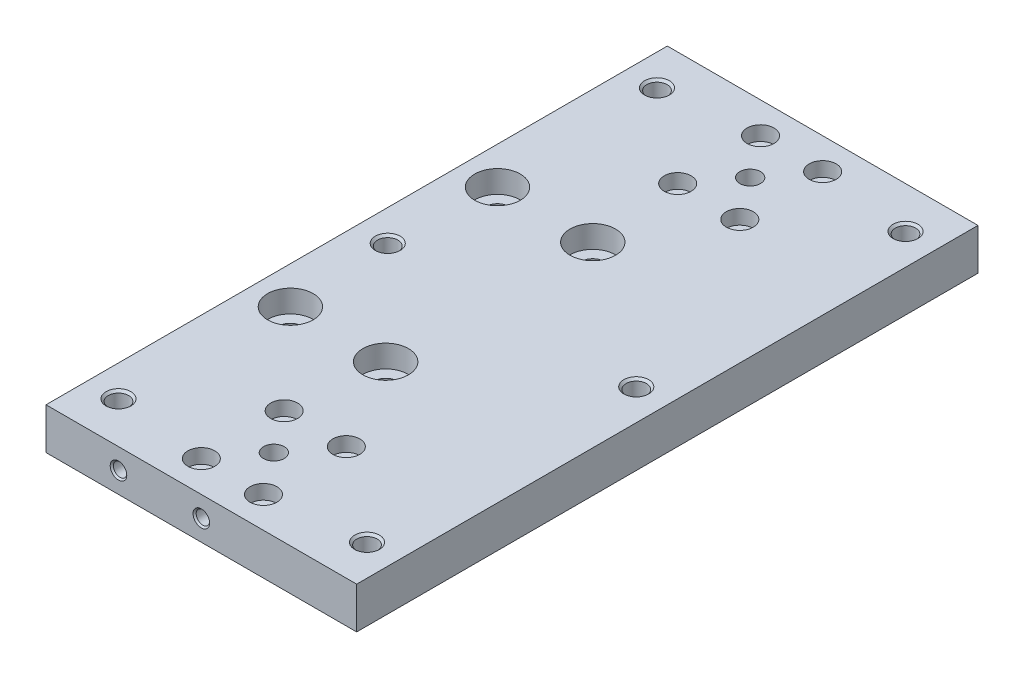
SolidWorks part; units mm, degrees
ref_plane "前视基准面" through (0, 0, 0) normal (0, 0, 1) x (1, 0, 0)
ref_plane "上视基准面" through (0, 0, 0) normal (0, 1, 0) x (1, 0, 0)
ref_plane "右视基准面" through (0, 0, 0) normal (1, 0, 0) x (0, 0, -1)
sketch "草图1" plane through (0, 0, 0) normal (0, 0, 1) x (1, 0, 0)
  line L0 (-37.5, 0) -> (37.5, 0)
  line L1 (37.5, 0) -> (37.5, 10)
  line L2 (37.5, 10) -> (-37.5, 10)
  line L3 (-37.5, 10) -> (-37.5, 0)
extrude "凸台-拉伸1" add sketch "草图1" against normal blind 75 and the other way blind 75
ref_plane "基准面4" through (0, 0, 57.5) normal (0, 0, 1) x (1, 0, 0)
sketch "草图2" plane through (0, 0, 57.5) normal (0, 0, 1) x (1, 0, 0)
  line L0 (0, 0) -> (-2.5, 0)
  line L1 (-2.5, 0) -> (-2.5, 10)
  line L2 (-2.5, 10) -> (0, 10)
  line L3 (0, 10) -> (0, 0)
  line L4 (0, 10) -> (0, 0) construction
revolve "切除-旋转1" cut sketch "草图2" angle 360 about L4 reverse direction yes
ref_plane "基准面5" through (0, 0, -57.5) normal (0, 0, 1) x (1, 0, 0)
sketch "草图3" plane through (0, 0, -57.5) normal (0, 0, 1) x (1, 0, 0)
  line L0 (0, 0) -> (-2.5, 0)
  line L1 (-2.5, 0) -> (-2.5, 10)
  line L2 (-2.5, 10) -> (0, 10)
  line L3 (0, 10) -> (0, 0)
  line L4 (0, 10) -> (0, 0) construction
revolve "切除-旋转2" cut sketch "草图3" angle 360 about L4 reverse direction yes
ref_plane "基准面6" through (0, 0, 67.5) normal (0, 0, 1) x (1, 0, 0)
sketch "草图4" plane through (0, 0, 67.5) normal (0, 0, 1) x (1, 0, 0)
  line L0 (-7.5, 0) -> (-9.25, 0)
  line L1 (-9.25, 0) -> (-9.25, 6.5)
  line L2 (-9.25, 6.5) -> (-10.75, 6.5)
  line L3 (-10.75, 6.5) -> (-10.75, 10)
  line L4 (-10.75, 10) -> (-7.5, 10)
  line L5 (-7.5, 10) -> (-7.5, 0)
  line L6 (-7.5, 10) -> (-7.5, 0) construction
revolve "切除-旋转3" cut sketch "草图4" angle 360 about L6 reverse direction yes
ref_plane "基准面7" through (0, 0, -47.5) normal (0, 0, 1) x (1, 0, 0)
ref_plane "基准面8" through (0, 0, -47.5) normal (0, 0, 1) x (1, 0, 0)
ref_plane "基准面9" through (0, 0, -67.5) normal (0, 0, 1) x (1, 0, 0)
ref_plane "基准面10" through (0, 0, -67.5) normal (0, 0, 1) x (1, 0, 0)
ref_plane "基准面11" through (0, 0, 47.5) normal (0, 0, 1) x (1, 0, 0)
ref_plane "基准面12" through (0, 0, 47.5) normal (0, 0, 1) x (1, 0, 0)
ref_plane "基准面13" through (0, 0, 67.5) normal (0, 0, 1) x (1, 0, 0)
sketch "草图6" plane through (0, 0, -47.5) normal (0, 0, 1) x (1, 0, 0)
  line L0 (7.5, 0) -> (5.75, 0)
  line L1 (5.75, 0) -> (5.75, 6.5)
  line L2 (5.75, 6.5) -> (4.25, 6.5)
  line L3 (4.25, 6.5) -> (4.25, 10)
  line L4 (4.25, 10) -> (7.5, 10)
  line L5 (7.5, 10) -> (7.5, 0)
  line L6 (7.5, 10) -> (7.5, 0) construction
sketch "草图7" plane through (0, 0, -47.5) normal (0, 0, 1) x (1, 0, 0)
  line L0 (-7.5, 0) -> (-9.25, 0)
  line L1 (-9.25, 0) -> (-9.25, 6.5)
  line L2 (-9.25, 6.5) -> (-10.75, 6.5)
  line L3 (-10.75, 6.5) -> (-10.75, 10)
  line L4 (-10.75, 10) -> (-7.5, 10)
  line L5 (-7.5, 10) -> (-7.5, 0)
  line L6 (-7.5, 10) -> (-7.5, 0) construction
sketch "草图8" plane through (0, 0, -67.5) normal (0, 0, 1) x (1, 0, 0)
  line L0 (7.5, 0) -> (5.75, 0)
  line L1 (5.75, 0) -> (5.75, 6.5)
  line L2 (5.75, 6.5) -> (4.25, 6.5)
  line L3 (4.25, 6.5) -> (4.25, 10)
  line L4 (4.25, 10) -> (7.5, 10)
  line L5 (7.5, 10) -> (7.5, 0)
  line L6 (7.5, 10) -> (7.5, 0) construction
sketch "草图9" plane through (0, 0, -67.5) normal (0, 0, 1) x (1, 0, 0)
  line L0 (-7.5, 0) -> (-9.25, 0)
  line L1 (-9.25, 0) -> (-9.25, 6.5)
  line L2 (-9.25, 6.5) -> (-10.75, 6.5)
  line L3 (-10.75, 6.5) -> (-10.75, 10)
  line L4 (-10.75, 10) -> (-7.5, 10)
  line L5 (-7.5, 10) -> (-7.5, 0)
  line L6 (-7.5, 10) -> (-7.5, 0) construction
sketch "草图10" plane through (0, 0, 47.5) normal (0, 0, 1) x (1, 0, 0)
  line L0 (7.5, 0) -> (5.75, 0)
  line L1 (5.75, 0) -> (5.75, 6.5)
  line L2 (5.75, 6.5) -> (4.25, 6.5)
  line L3 (4.25, 6.5) -> (4.25, 10)
  line L4 (4.25, 10) -> (7.5, 10)
  line L5 (7.5, 10) -> (7.5, 0)
  line L6 (7.5, 10) -> (7.5, 0) construction
sketch "草图11" plane through (0, 0, 47.5) normal (0, 0, 1) x (1, 0, 0)
  line L0 (-7.5, 0) -> (-9.25, 0)
  line L1 (-9.25, 0) -> (-9.25, 6.5)
  line L2 (-9.25, 6.5) -> (-10.75, 6.5)
  line L3 (-10.75, 6.5) -> (-10.75, 10)
  line L4 (-10.75, 10) -> (-7.5, 10)
  line L5 (-7.5, 10) -> (-7.5, 0)
  line L6 (-7.5, 10) -> (-7.5, 0) construction
sketch "草图12" plane through (0, 0, 67.5) normal (0, 0, 1) x (1, 0, 0)
  line L0 (7.5, 0) -> (5.75, 0)
  line L1 (5.75, 0) -> (5.75, 6.5)
  line L2 (5.75, 6.5) -> (4.25, 6.5)
  line L3 (4.25, 6.5) -> (4.25, 10)
  line L4 (4.25, 10) -> (7.5, 10)
  line L5 (7.5, 10) -> (7.5, 0)
  line L6 (7.5, 10) -> (7.5, 0) construction
revolve "切除-旋转4" cut sketch "草图6" angle 360 about L6 reverse direction yes
revolve "切除-旋转5" cut sketch "草图7" angle 360 about L6 reverse direction yes
revolve "切除-旋转6" cut sketch "草图8" angle 360 about L6 reverse direction yes
revolve "切除-旋转7" cut sketch "草图9" angle 360 about L6 reverse direction yes
revolve "切除-旋转8" cut sketch "草图10" angle 360 about L6 reverse direction yes
revolve "切除-旋转9" cut sketch "草图11" angle 360 about L6 reverse direction yes
revolve "切除-旋转10" cut sketch "草图12" angle 360 about L6 reverse direction yes
ref_plane "基准面14" through (0, 6.5, 0) normal (0, 1, 0) x (1, 0, 0)
ref_plane "基准面15" through (-28.5, 0, 0) normal (1, 0, 0) x (0, 0, -1)
sketch "草图13" plane through (-28.5, 0, 0) normal (1, 0, 0) x (0, 0, -1)
  line L0 (-25, 0) -> (-27.75, 0)
  line L1 (-27.75, 0) -> (-27.75, 4.6)
  line L2 (-27.75, 4.6) -> (-30.5, 4.6)
  line L3 (-30.5, 4.6) -> (-30.5, 10)
  line L4 (-30.5, 10) -> (-25, 10)
  line L5 (-25, 10) -> (-25, 0)
  line L6 (-25, 10) -> (-25, 0) construction
revolve "切除-旋转11" cut sketch "草图13" angle 360 about L6 reverse direction yes
sketch "草图14" plane through (0, 0, 0) normal (0, 1, 0) x (1, 0, 0)
  line L0 (-28.5, -25) -> (971.5, -25)
  line L1 (-28.5, -25) -> (-28.5, 975)
pattern_linear "阵列(线性)2" count 2 spacing 23 along (1, 0, 0) count 2 spacing 50 along (0, 0, -1) of "切除-旋转11"
ref_plane "基准面16" through (0, 4.6, 0) normal (0, 1, 0) x (1, 0, 0)
ref_plane "基准面17" through (0, 2.5, 0) normal (0, 1, 0) x (1, 0, 0)
sketch "草图15" plane through (0, 2.5, 0) normal (0, 1, 0) x (1, 0, 0)
  line L0 (-36.5, 32.5) -> (-36.5, -32.5)
  line L1 (-36.5, -32.5) -> (2.5, -32.5)
  line L2 (2.5, -32.5) -> (2.5, 32.5)
  line L3 (2.5, 32.5) -> (-36.5, 32.5)
extrude "切除-拉伸1" cut sketch "草图15" against normal blind 32.5
ref_plane "基准面18" through (0, 0, 0) normal (1, 0, 0) x (0, 0, -1)
sketch "草图16" plane through (0, 0, 0) normal (1, 0, 0) x (0, 0, -1)
  line L0 (-75, 5) -> (-75, 7)
  line L1 (-75, 7) -> (-74.621, 6.621)
  line L2 (-74.621, 6.621) -> (-65.4, 6.621)
  line L3 (-65.4, 6.621) -> (-64.4641, 5)
  line L4 (-64.4641, 5) -> (-75, 5)
  line L5 (-64.4641, 5) -> (-75, 5) construction
revolve "切除-旋转12" cut sketch "草图16" angle 360 about L5 reverse direction yes
cosmetic thread "装饰螺纹线1" parameters "D1"=8, "D2"=4
sketch "草图17" plane through (0, 0, 0) normal (1, 0, 0) x (0, 0, -1)
  line L0 (75, 5) -> (75, 3)
  line L1 (75, 3) -> (74.621, 3.379)
  line L2 (74.621, 3.379) -> (65.4, 3.379)
  line L3 (65.4, 3.379) -> (64.4641, 5)
  line L4 (64.4641, 5) -> (75, 5)
  line L5 (64.4641, 5) -> (75, 5) construction
revolve "切除-旋转13" cut sketch "草图17" angle 360 about L5 reverse direction yes
cosmetic thread "装饰螺纹线2" parameters "D1"=8, "D2"=4
ref_plane "基准面19" through (-20, 0, 0) normal (1, 0, 0) x (0, 0, -1)
sketch "草图18" plane through (-20, 0, 0) normal (1, 0, 0) x (0, 0, -1)
  line L0 (-75, 5) -> (-75, 7)
  line L1 (-75, 7) -> (-74.621, 6.621)
  line L2 (-74.621, 6.621) -> (-65.4, 6.621)
  line L3 (-65.4, 6.621) -> (-64.4641, 5)
  line L4 (-64.4641, 5) -> (-75, 5)
  line L5 (-64.4641, 5) -> (-75, 5) construction
sketch "草图19" plane through (-20, 0, 0) normal (1, 0, 0) x (0, 0, -1)
  line L0 (75, 5) -> (75, 3)
  line L1 (75, 3) -> (74.621, 3.379)
  line L2 (74.621, 3.379) -> (65.4, 3.379)
  line L3 (65.4, 3.379) -> (64.4641, 5)
  line L4 (64.4641, 5) -> (75, 5)
  line L5 (64.4641, 5) -> (75, 5) construction
revolve "切除-旋转14" cut sketch "草图18" angle 360 about L5 reverse direction yes
cosmetic thread "装饰螺纹线3" parameters "D1"=8, "D2"=4
revolve "切除-旋转15" cut sketch "草图19" angle 360 about L5 reverse direction yes
cosmetic thread "装饰螺纹线4" parameters "D1"=8, "D2"=4
ref_plane "基准面20" through (30, 0, 0) normal (1, 0, 0) x (0, 0, -1)
sketch "草图20" plane through (30, 0, 0) normal (1, 0, 0) x (0, 0, -1)
  line L0 (-65, 10) -> (-62, 10)
  line L1 (-62, 10) -> (-62.5415, 9.4585)
  line L2 (-62.5415, 9.4585) -> (-62.5415, 0.5415)
  line L3 (-62.5415, 0.5415) -> (-62, 0)
  line L4 (-62, 0) -> (-65, 0)
  line L5 (-65, 0) -> (-65, 10)
  line L6 (-65, 0) -> (-65, 10) construction
revolve "切除-旋转16" cut sketch "草图20" angle 360 about L6 reverse direction yes
cosmetic thread "装饰螺纹线5" parameters "D1"=10, "D2"=6
sketch "草图21" plane through (30, 0, 0) normal (1, 0, 0) x (0, 0, -1)
  line L0 (65, 10) -> (68, 10)
  line L1 (68, 10) -> (67.4585, 9.4585)
  line L2 (67.4585, 9.4585) -> (67.4585, 0.5415)
  line L3 (67.4585, 0.5415) -> (68, 0)
  line L4 (68, 0) -> (65, 0)
  line L5 (65, 0) -> (65, 10)
  line L6 (65, 0) -> (65, 10) construction
sketch "草图22" plane through (30, 0, 0) normal (1, 0, 0) x (0, 0, -1)
  line L0 (0, 10) -> (3, 10)
  line L1 (3, 10) -> (2.4585, 9.4585)
  line L2 (2.4585, 9.4585) -> (2.4585, 0.5415)
  line L3 (2.4585, 0.5415) -> (3, 0)
  line L4 (3, 0) -> (0, 0)
  line L5 (0, 0) -> (0, 10)
  line L6 (0, 0) -> (0, 10) construction
revolve "切除-旋转17" cut sketch "草图21" angle 360 about L6 reverse direction yes
cosmetic thread "装饰螺纹线6" parameters "D1"=10, "D2"=6
revolve "切除-旋转18" cut sketch "草图22" angle 360 about L6 reverse direction yes
cosmetic thread "装饰螺纹线7" parameters "D1"=10, "D2"=6
ref_plane "基准面21" through (-30, 0, 0) normal (1, 0, 0) x (0, 0, -1)
sketch "草图23" plane through (-30, 0, 0) normal (1, 0, 0) x (0, 0, -1)
  line L0 (-65, 10) -> (-62, 10)
  line L1 (-62, 10) -> (-62.5415, 9.4585)
  line L2 (-62.5415, 9.4585) -> (-62.5415, 0.5415)
  line L3 (-62.5415, 0.5415) -> (-62, 0)
  line L4 (-62, 0) -> (-65, 0)
  line L5 (-65, 0) -> (-65, 10)
  line L6 (-65, 0) -> (-65, 10) construction
revolve "切除-旋转19" cut sketch "草图23" angle 360 about L6 reverse direction yes
cosmetic thread "装饰螺纹线8" parameters "D1"=10, "D2"=6
sketch "草图24" plane through (-30, 0, 0) normal (1, 0, 0) x (0, 0, -1)
  line L0 (65, 10) -> (68, 10)
  line L1 (68, 10) -> (67.4585, 9.4585)
  line L2 (67.4585, 9.4585) -> (67.4585, 0.5415)
  line L3 (67.4585, 0.5415) -> (68, 0)
  line L4 (68, 0) -> (65, 0)
  line L5 (65, 0) -> (65, 10)
  line L6 (65, 0) -> (65, 10) construction
revolve "切除-旋转20" cut sketch "草图24" angle 360 about L6 reverse direction yes
cosmetic thread "装饰螺纹线9" parameters "D1"=10, "D2"=6
sketch "草图25" plane through (-30, 0, 0) normal (1, 0, 0) x (0, 0, -1)
  line L0 (0, 10) -> (3, 10)
  line L1 (3, 10) -> (2.4585, 9.4585)
  line L2 (2.4585, 9.4585) -> (2.4585, 3.0415)
  line L3 (2.4585, 3.0415) -> (3, 2.5)
  line L4 (3, 2.5) -> (0, 2.5)
  line L5 (0, 2.5) -> (0, 10)
  line L6 (0, 2.5) -> (0, 10) construction
revolve "切除-旋转21" cut sketch "草图25" angle 360 about L6 reverse direction yes
cosmetic thread "装饰螺纹线10" parameters "D1"=7.5, "D2"=6
ref_plane "table_to_frame XY" through (0, 0, 0) normal (1, 0, 0) x (0, 0, -1)
ref_plane "table_to_frame XZ" through (0, 0, 0) normal (0, -1, 0) x (-1, 0, 0)
ref_plane "table_to_frame YZ" through (0, 0, 0) normal (0, 0, -1) x (-1, 0, 0)
ref_axis "table_to_frame X" through (0, 0, 80.9) along (0, 0, -1)
ref_axis "table_to_frame Y" through (0, -50, 0) along (0, 1, 0)
ref_axis "table_to_frame Z" through (80.9, 0, 0) along (-1, 0, 0)
sketch3d "table_to_frame"
  point P0 (0, 0, 0)
ref_plane "block_nut 3 XY" through (0, 6.5, 0) normal (0, 1, 0) x (1, 0, 0)
ref_plane "block_nut 3 XZ" through (0, 0, 47.5) normal (0, 0, 1) x (1, 0, 0)
ref_plane "block_nut 3 YZ" through (-7.5, 0, 0) normal (1, 0, 0) x (0, 0, -1)
ref_axis "block_nut 3 X" through (-80.9, 6.5, 47.5) along (1, 0, 0)
ref_axis "block_nut 3 Y" through (-7.5, 6.5, 50) along (0, 0, -1)
ref_axis "block_nut 3 Z" through (-7.5, 50, 47.5) along (0, -1, 0)
sketch3d "block_nut 3"
  point P0 (-7.5, 6.5, 47.5)
ref_plane "block_nut 2 XY" through (0, 6.5, 0) normal (0, 1, 0) x (1, 0, 0)
ref_plane "block_nut 2 XZ" through (0, 0, 67.5) normal (0, 0, 1) x (1, 0, 0)
ref_plane "block_nut 2 YZ" through (7.5, 0, 0) normal (1, 0, 0) x (0, 0, -1)
ref_axis "block_nut 2 X" through (-80.9, 6.5, 67.5) along (1, 0, 0)
ref_axis "block_nut 2 Y" through (7.5, 6.5, 50) along (0, 0, -1)
ref_axis "block_nut 2 Z" through (7.5, 50, 67.5) along (0, -1, 0)
sketch3d "block_nut 2"
  point P0 (7.5, 6.5, 67.5)
ref_plane "block_nut 1 XY" through (0, 6.5, 0) normal (0, 1, 0) x (1, 0, 0)
ref_plane "block_nut 1 XZ" through (0, 0, 67.5) normal (0, 0, 1) x (1, 0, 0)
ref_plane "block_nut 1 YZ" through (-7.5, 0, 0) normal (1, 0, 0) x (0, 0, -1)
ref_axis "block_nut 1 X" through (-80.9, 6.5, 67.5) along (1, 0, 0)
ref_axis "block_nut 1 Y" through (-7.5, 6.5, 50) along (0, 0, -1)
ref_axis "block_nut 1 Z" through (-7.5, 50, 67.5) along (0, -1, 0)
sketch3d "block_nut 1"
  point P0 (-7.5, 6.5, 67.5)
ref_plane "block_nut 7 XY" through (0, 6.5, 0) normal (0, 1, 0) x (1, 0, 0)
ref_plane "block_nut 7 XZ" through (0, 0, -47.5) normal (0, 0, 1) x (1, 0, 0)
ref_plane "block_nut 7 YZ" through (-7.5, 0, 0) normal (1, 0, 0) x (0, 0, -1)
ref_axis "block_nut 7 X" through (-80.9, 6.5, -47.5) along (1, 0, 0)
ref_axis "block_nut 7 Y" through (-7.5, 6.5, 50) along (0, 0, -1)
ref_axis "block_nut 7 Z" through (-7.5, 50, -47.5) along (0, -1, 0)
sketch3d "block_nut 7"
  point P0 (-7.5, 6.5, -47.5)
ref_plane "block_nut 6 XY" through (0, 6.5, 0) normal (0, 1, 0) x (1, 0, 0)
ref_plane "block_nut 6 XZ" through (0, 0, -67.5) normal (0, 0, 1) x (1, 0, 0)
ref_plane "block_nut 6 YZ" through (7.5, 0, 0) normal (1, 0, 0) x (0, 0, -1)
ref_axis "block_nut 6 X" through (-80.9, 6.5, -67.5) along (1, 0, 0)
ref_axis "block_nut 6 Y" through (7.5, 6.5, 50) along (0, 0, -1)
ref_axis "block_nut 6 Z" through (7.5, 50, -67.5) along (0, -1, 0)
sketch3d "block_nut 6"
  point P0 (7.5, 6.5, -67.5)
ref_plane "block_nut 5 XY" through (0, 6.5, 0) normal (0, 1, 0) x (1, 0, 0)
ref_plane "block_nut 5 XZ" through (0, 0, -67.5) normal (0, 0, 1) x (1, 0, 0)
ref_plane "block_nut 5 YZ" through (-7.5, 0, 0) normal (1, 0, 0) x (0, 0, -1)
ref_axis "block_nut 5 X" through (-80.9, 6.5, -67.5) along (1, 0, 0)
ref_axis "block_nut 5 Y" through (-7.5, 6.5, 50) along (0, 0, -1)
ref_axis "block_nut 5 Z" through (-7.5, 50, -67.5) along (0, -1, 0)
sketch3d "block_nut 5"
  point P0 (-7.5, 6.5, -67.5)
ref_plane "block_nut 4 XY" through (0, 6.5, 0) normal (0, 1, 0) x (1, 0, 0)
ref_plane "block_nut 4 XZ" through (0, 0, 47.5) normal (0, 0, 1) x (1, 0, 0)
ref_plane "block_nut 4 YZ" through (7.5, 0, 0) normal (1, 0, 0) x (0, 0, -1)
ref_axis "block_nut 4 X" through (-80.9, 6.5, 47.5) along (1, 0, 0)
ref_axis "block_nut 4 Y" through (7.5, 6.5, 50) along (0, 0, -1)
ref_axis "block_nut 4 Z" through (7.5, 50, 47.5) along (0, -1, 0)
sketch3d "block_nut 4"
  point P0 (7.5, 6.5, 47.5)
ref_plane "block_nut 8 XY" through (0, 6.5, 0) normal (0, 1, 0) x (1, 0, 0)
ref_plane "block_nut 8 XZ" through (0, 0, -47.5) normal (0, 0, 1) x (1, 0, 0)
ref_plane "block_nut 8 YZ" through (7.5, 0, 0) normal (1, 0, 0) x (0, 0, -1)
ref_axis "block_nut 8 X" through (-80.9, 6.5, -47.5) along (1, 0, 0)
ref_axis "block_nut 8 Y" through (7.5, 6.5, 50) along (0, 0, -1)
ref_axis "block_nut 8 Z" through (7.5, 50, -47.5) along (0, -1, 0)
sketch3d "block_nut 8"
  point P0 (7.5, 6.5, -47.5)
ref_plane "nut_for_bracket 4 XY" through (0, 4.6, 0) normal (0, 1, 0) x (1, 0, 0)
ref_plane "nut_for_bracket 4 XZ" through (0, 0, -25) normal (0, 0, 1) x (1, 0, 0)
ref_plane "nut_for_bracket 4 YZ" through (-5.5, 0, 0) normal (1, 0, 0) x (0, 0, -1)
ref_axis "nut_for_bracket 4 X" through (-80.9, 4.6, -25) along (1, 0, 0)
ref_axis "nut_for_bracket 4 Y" through (-5.5, 4.6, 50) along (0, 0, -1)
ref_axis "nut_for_bracket 4 Z" through (-5.5, 50, -25) along (0, -1, 0)
sketch3d "nut_for_bracket 4"
  point P0 (-5.5, 4.6, -25)
ref_plane "nut_for_bracket 3 XY" through (0, 4.6, 0) normal (0, 1, 0) x (1, 0, 0)
ref_plane "nut_for_bracket 3 XZ" through (0, 0, -25) normal (0, 0, 1) x (1, 0, 0)
ref_plane "nut_for_bracket 3 YZ" through (-28.5, 0, 0) normal (1, 0, 0) x (0, 0, -1)
ref_axis "nut_for_bracket 3 X" through (-80.9, 4.6, -25) along (1, 0, 0)
ref_axis "nut_for_bracket 3 Y" through (-28.5, 4.6, 50) along (0, 0, -1)
ref_axis "nut_for_bracket 3 Z" through (-28.5, 50, -25) along (0, -1, 0)
sketch3d "nut_for_bracket 3"
  point P0 (-28.5, 4.6, -25)
ref_plane "nut_for_bracket 2 XY" through (0, 4.6, 0) normal (0, 1, 0) x (1, 0, 0)
ref_plane "nut_for_bracket 2 XZ" through (0, 0, 25) normal (0, 0, 1) x (1, 0, 0)
ref_plane "nut_for_bracket 2 YZ" through (-5.5, 0, 0) normal (1, 0, 0) x (0, 0, -1)
ref_axis "nut_for_bracket 2 X" through (-80.9, 4.6, 25) along (1, 0, 0)
ref_axis "nut_for_bracket 2 Y" through (-5.5, 4.6, 50) along (0, 0, -1)
ref_axis "nut_for_bracket 2 Z" through (-5.5, 50, 25) along (0, -1, 0)
sketch3d "nut_for_bracket 2"
  point P0 (-5.5, 4.6, 25)
ref_plane "nut_for_bracket 1 XY" through (0, 4.6, 0) normal (0, 1, 0) x (1, 0, 0)
ref_plane "nut_for_bracket 1 XZ" through (0, 0, 25) normal (0, 0, 1) x (1, 0, 0)
ref_plane "nut_for_bracket 1 YZ" through (-28.5, 0, 0) normal (1, 0, 0) x (0, 0, -1)
ref_axis "nut_for_bracket 1 X" through (-80.9, 4.6, 25) along (1, 0, 0)
ref_axis "nut_for_bracket 1 Y" through (-28.5, 4.6, 50) along (0, 0, -1)
ref_axis "nut_for_bracket 1 Z" through (-28.5, 50, 25) along (0, -1, 0)
sketch3d "nut_for_bracket 1"
  point P0 (-28.5, 4.6, 25)
